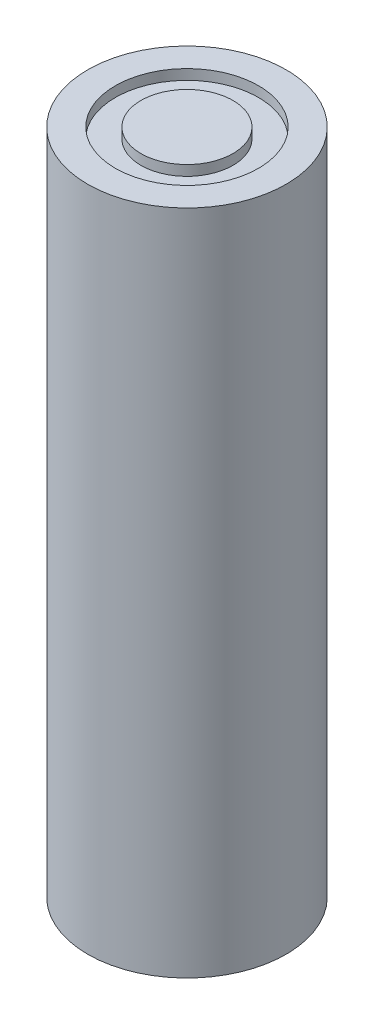
SolidWorks part; units mm, degrees
ref_plane "Front Plane" through (0, 0, 0) normal (0, 0, 1) x (1, 0, 0)
ref_plane "Top Plane" through (0, 0, 0) normal (0, 1, 0) x (1, 0, 0)
ref_plane "Right Plane" through (0, 0, 0) normal (1, 0, 0) x (0, 0, -1)
sketch "Sketch2" plane through (0, 0, 0) normal (0, 1, 0) x (1, 0, 0)
  circle A0 centre (0, 0) radius 9.7
  dimension "D1" = 19.4
extrude "Boss-Extrude1" add sketch "Sketch2" along normal blind 65.2
sketch "Sketch3" plane through (0, 65.2, 0) normal (0, 1, 0) x (1, 0, 0)
  circle A0 centre (0, 0) radius 7
  circle A1 centre (0, 0) radius 4.5
  dimension "D1" = 14
  dimension "D2" = 9
extrude "Cut-Extrude1" cut sketch "Sketch3" against normal blind 1
ref_axis "Axis1" through (0, 0, -10.23) along (0, 0, 1)
